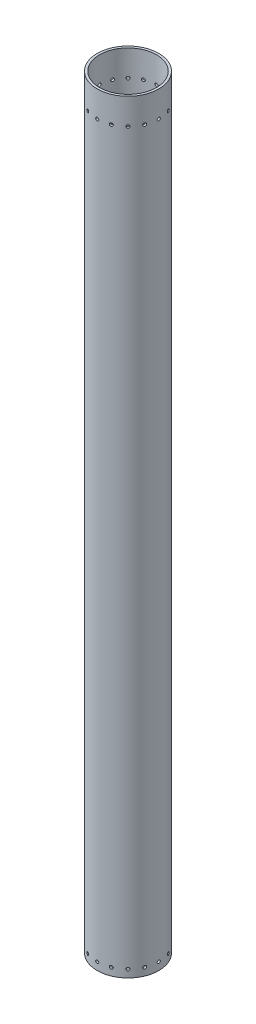
SolidWorks part; units mm, degrees
material "6061-T6 (SS)"
ref_plane "Front Plane" through (0, 0, 0) normal (0, 0, 1) x (1, 0, 0)
ref_plane "Top Plane" through (0, 0, 0) normal (0, 1, 0) x (1, 0, 0)
ref_plane "Right Plane" through (0, 0, 0) normal (1, 0, 0) x (0, 0, -1)
sketch "Sketch1" plane through (0, 0, 0) normal (0, 1, 0) x (1, 0, 0)
  circle A0 centre (0, 0) radius 63.5
  circle A1 centre (0, 0) radius 58.7375
extrude "CasingBody" add sketch "Sketch1" along normal blind 1574.8
ref_plane "HoleFacePlane" through (0, 0, 63.5) normal (0, 0, 1) x (1, 0, 0)
sketch "NozzleReference" plane through (0, 0, 63.5) normal (0, 0, 1) x (1, 0, 0)
  line L0 (-63.5, 0) -> (63.5, 0) construction
  point P4 (0, 15.875)
  dimension "D1" = 15.875
hole_wizard "NozzleHoles" positions "Sketch15" profile "Sketch16" hole size "1/4" standard "ANSI Inch" end condition through all
sketch "Sketch15" plane through (0, 0, 63.5) normal (0, 0, 1) x (1, 0, 0)
  point P0 (0, 15.875)
sketch "Sketch16" plane through (0, 15.875, 63.5) normal (1, 0, 0) x (0, -1, 0)
  line L0 (0, 0) -> (0, 127)
  line L1 (0, 127) -> (3.175, 127)
  line L2 (3.175, 127) -> (3.175, 0)
  line L5 (3.175, 0) -> (0, 0)
  line L11 (0, -6.35) -> (0, 107.95) construction
  dimension "Thru Hole Dia." = 6.35
  dimension "Thru Hole Depth" = 127
sketch "Centerline" plane through (0, 0, 0) normal (0, 0, 1) x (1, 0, 0)
  line L0 (0, 0) -> (0, 1651) construction
pattern_circular "NozzleHolePattern" count 16 over 360 about axis through (0, 0, 0) along (0, 1, 0) of "NozzleHoles"
ref_plane "NozzleReferencePlane" through (0, 15.875, 0) normal (0, 1, 0) x (1, 0, 0)
sketch "ForwardClosureReference" plane through (0, 0, 63.5) normal (0, 0, 1) x (1, 0, 0)
  line L0 (63.5, 1574.8) -> (-63.5, 1574.8) construction
  point P6 (0, 1520.825)
  dimension "D1" = 53.975
ref_plane "ForwardClosureReferencePlane" through (0, 1520.825, 0) normal (0, 1, 0) x (1, 0, 0)
hole_wizard "ClosureHoles" positions "Sketch17" profile "Sketch18" hole size "1/4" standard "ANSI Inch" end condition through all
sketch "Sketch17" plane through (0, 0, 63.5) normal (0, 0, 1) x (1, 0, 0)
  point P0 (0, 1520.825)
sketch "Sketch18" plane through (0, 1520.825, 63.5) normal (1, 0, 0) x (0, -1, 0)
  line L0 (0, 0) -> (0, 127)
  line L1 (0, 127) -> (3.175, 127)
  line L2 (3.175, 127) -> (3.175, 0)
  line L5 (3.175, 0) -> (0, 0)
  line L11 (0, -6.35) -> (0, 107.95) construction
  dimension "Thru Hole Dia." = 6.35
  dimension "Thru Hole Depth" = 127
pattern_circular "ClosureHolePattern" count 16 over 360 about axis through (0, 0, 0) along (0, 1, 0) of "ClosureHoles" reverse direction yes
